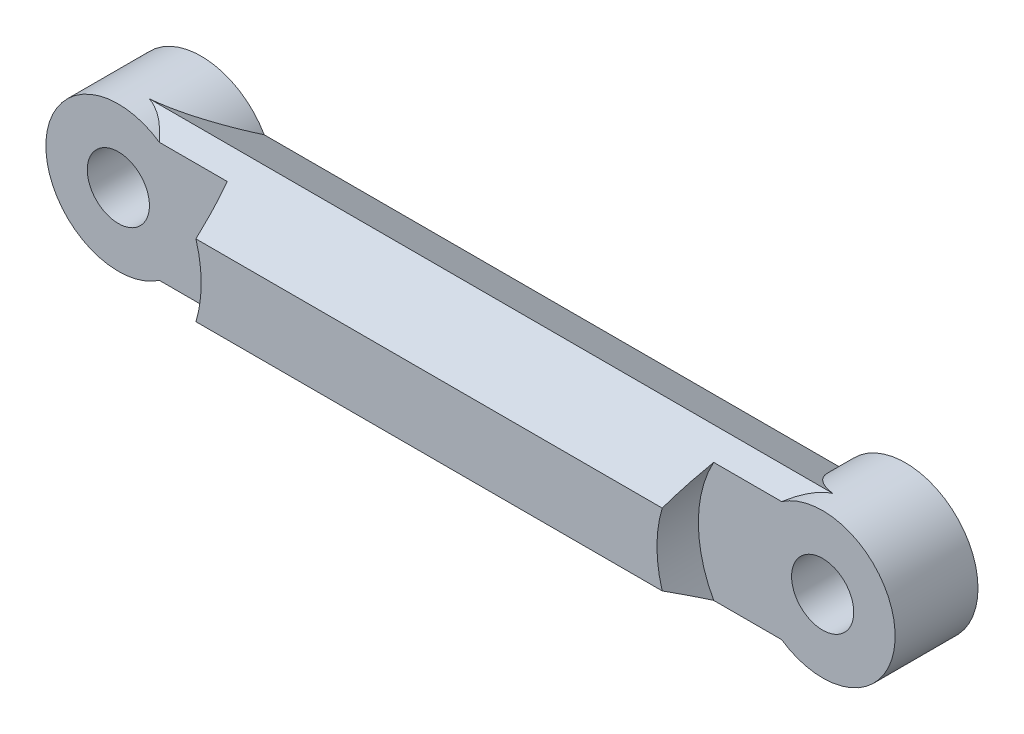
SolidWorks part; units mm, degrees
ref_plane "Front Plane" through (0, 0, 0) normal (0, 0, 1) x (1, 0, 0)
ref_plane "Top Plane" through (0, 0, 0) normal (0, 1, 0) x (1, 0, 0)
ref_plane "Right Plane" through (0, 0, 0) normal (1, 0, 0) x (0, 0, -1)
sketch "Sketch1" plane through (0, 0, 0) normal (0, 0, 1) x (1, 0, 0)
  line L0 (-17, 0) -> (17, 0) construction
  circle A0 centre (-17, 0) radius 1.5
  circle A1 centre (17, 0) radius 1.5
  circle A6 centre (-17, 0) radius 3.5
  circle A7 centre (17, 0) radius 3.5
  dimension "D2" = 3
  dimension "D3" = 7
  dimension "D1" = 34
extrude "Boss-Extrude1" add sketch "Sketch1" along normal mid plane 6
sketch "Sketch2" plane through (0, 0, 0) normal (1, 0, 0) x (0, 0, -1)
  line L0 (0, 0) -> (0, 3.4641) construction
  line L1 (-3, 1.7321) -> (-3, -1.7321)
  line L2 (-3, -1.7321) -> (0, -3.4641)
  line L3 (0, -3.4641) -> (3, -1.7321)
  line L4 (3, -1.7321) -> (3, 1.7321)
  line L5 (3, 1.7321) -> (0, 3.4641)
  line L6 (0, 3.4641) -> (-3, 1.7321)
  circle A0 centre (0, 0) radius 3 construction
  dimension "D1" = 6
extrude "Boss-Extrude2" add sketch "Sketch2" against normal up to surface and the other way up to surface up to face at (-13.5, 0, 3) other way up to face at (20.5, 0, 3)
sketch "Sketch3" plane through (0, 0, 3) normal (0, 0, 1) x (1, 0, 0)
  line L0 (0, 0) -> (0, 4.682) construction
  circle A0 centre (-17, 0) radius 6
  circle A1 centre (17, 0) radius 6
  dimension "D1" = 12
extrude "Cut-Extrude1" cut sketch "Sketch3" against normal blind 2
